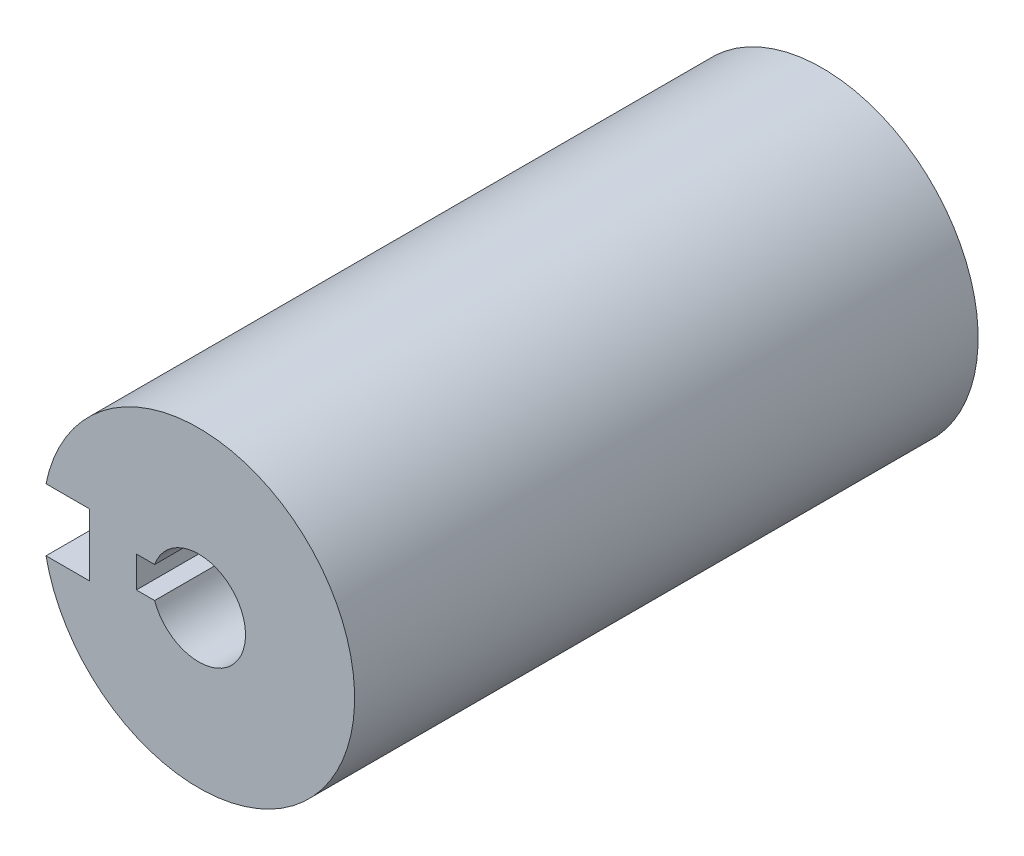
SolidWorks part; units mm, degrees
ref_plane "Front Plane" through (0, 0, 0) normal (0, 0, 1) x (1, 0, 0)
ref_plane "Top Plane" through (0, 0, 0) normal (0, 1, 0) x (1, 0, 0)
ref_plane "Right Plane" through (0, 0, 0) normal (1, 0, 0) x (0, 0, -1)
sketch "Sketch5" plane through (0, 0, 0) normal (0, 0, 1) x (1, 0, 0)
  circle A0 centre (0, 0) radius 5
  circle A1 centre (0, 0) radius 1.5
  dimension "D1" = 10
  dimension "D2" = 3
extrude "Boss-Extrude2" add sketch "Sketch5" along normal blind 20
sketch "Sketch6" plane through (0, 0, 20) normal (0, 0, 1) x (1, 0, 0)
  line L1 (-2, 0.5) -> (-1, 0.5)
  line L2 (-2, 0.5) -> (-2, -0.5)
  line L3 (-2, -0.5) -> (-1, -0.5)
  line L4 (-1, 0.5) -> (-1, -0.5)
  line L5 (-2, 0.5) -> (-1, -0.5) construction
  line L6 (-2, -0.5) -> (-1, 0.5) construction
  circle A0 centre (0, 0) radius 1.5 construction
  point P0 (-1.5, 0)
  dimension "D1" = 1
  dimension "D2" = 1
extrude "Cut-Extrude4" cut sketch "Sketch6" against normal blind 12
sketch "Sketch7" plane through (0, 0, 20) normal (0, 0, 1) x (1, 0, 0)
  line L1 (-5.5, 0.5) -> (-4.5, 0.5)
  line L2 (-5.5, 0.5) -> (-5.5, -0.5)
  line L3 (-5.5, -0.5) -> (-4.5, -0.5)
  line L4 (-4.5, 0.5) -> (-4.5, -0.5)
  line L5 (-5.5, 0.5) -> (-4.5, -0.5) construction
  line L6 (-5.5, -0.5) -> (-4.5, 0.5) construction
  circle A0 centre (0, 0) radius 5 construction
  point P0 (-5, 0)
  dimension "D1" = 1
  dimension "D2" = 1
extrude "Cut-Extrude6" cut sketch "Sketch7" against normal blind 4
sketch "Sketch8" plane through (0, 0, 0) normal (0, 0, -1) x (-1, 0, 0)
  line L1 (3.5, 1) -> (6.5, 1)
  line L2 (3.5, 1) -> (3.5, -1)
  line L3 (3.5, -1) -> (6.5, -1)
  line L4 (6.5, 1) -> (6.5, -1)
  line L5 (3.5, 1) -> (6.5, -1) construction
  line L6 (3.5, -1) -> (6.5, 1) construction
  circle A0 centre (0, 0) radius 5 construction
  point P0 (5, 0)
  dimension "D1" = 3
  dimension "D2" = 2
extrude "Cut-Extrude7" cut sketch "Sketch8" against normal blind 20
